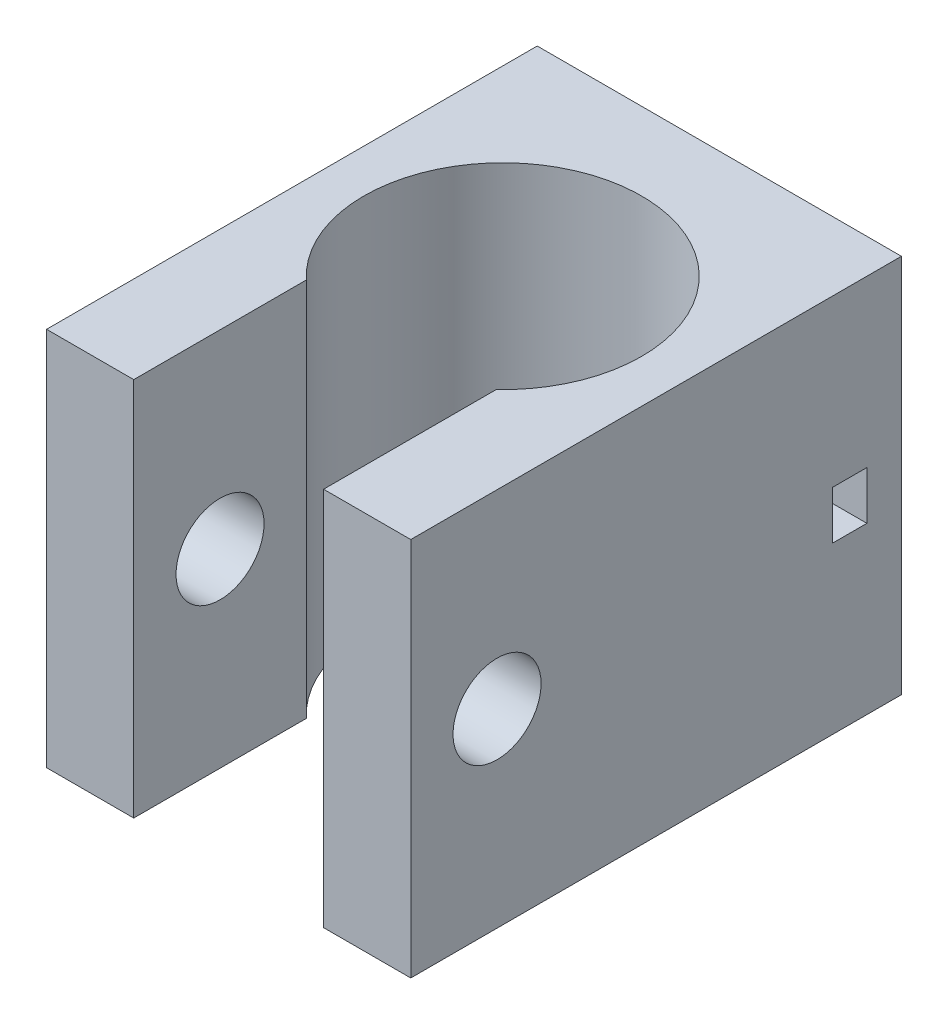
SolidWorks part; units mm, degrees
ref_plane "Front Plane" through (0, 0, 0) normal (0, 0, 1) x (1, 0, 0)
ref_plane "Top Plane" through (0, 0, 0) normal (0, 1, 0) x (1, 0, 0)
ref_plane "Right Plane" through (0, 0, 0) normal (1, 0, 0) x (0, 0, -1)
sketch "Sketch1" plane through (0, 0, 0) normal (0, 1, 0) x (1, 0, 0)
  line L0 (-5.5, -15) -> (-10.55, -15)
  line L1 (-10.55, -15) -> (-10.55, 13.4281)
  line L2 (-10.55, 13.4281) -> (10.55, 13.4281)
  line L3 (10.55, 13.4281) -> (10.55, -15)
  line L4 (10.55, -15) -> (5.5, -15)
  line L5 (5.5, -15) -> (5.5, -5)
  line L6 (-5.5, -15) -> (-5.5, -5)
  line L7 (-44.2539, 0) -> (44.2539, 0) construction
  line L8 (0, -44.7868) -> (0, 44.7868) construction
  arc A0 (-5.5, -5) -> (5.5, -5) centre (0, 0.8781) cw
  dimension "D1" = 8.05
  dimension "D2" = 11
  dimension "D3" = 10
  dimension "D4" = 10
  dimension "D5" = 21.1
  dimension "D6" = 12.55
  dimension "D7" = 15
  dimension "D8" = 10.55
extrude "Boss-Extrude1" add sketch "Sketch1" along normal mid plane 22
sketch "Sketch2" plane through (10.55, 0, 0) normal (1, 0, 0) x (0, 0, -1)
  line L0 (55, 0) -> (-55, 0) construction
  line L1 (-15, 11) -> (-15, -11) construction
  circle A0 centre (-10, 0) radius 2.55
  dimension "D1" = 5
  dimension "D2" = 5.1
extrude "Cut-Extrude1" cut sketch "Sketch2" against normal up to surface (21.1 mm away) up to face at (-10.55, 0, 0.7859)
sketch "Sketch4" plane through (10.55, 0, 0) normal (1, 0, 0) x (0, 0, -1)
  line L1 (9.4281, 1.4) -> (11.4281, 1.4)
  line L2 (9.4281, 1.4) -> (9.4281, -1.4)
  line L3 (9.4281, -1.4) -> (11.4281, -1.4)
  line L4 (11.4281, 1.4) -> (11.4281, -1.4)
  line L5 (-15, 11) -> (13.4281, 11) construction
  line L7 (13.4281, 11) -> (13.4281, -11) construction
  point P6 (10.4281, 1.4)
  dimension "D1" = 2
  dimension "D2" = 2.8
  dimension "D3" = 9.6
  dimension "D4" = 2
extrude "Cut-Extrude3" cut sketch "Sketch4" against normal up to surface (21.1 mm away) up to face at (-10.55, 0, 7.45)
sketch "Sketch5" plane through (0, 0, -13.4281) normal (0, 0, -1) x (-1, 0, 0)
  line L0 (10.55, 11) -> (10.55, -11) construction
  line L1 (-2.5, 8.5) -> (2.5, 8.5)
  line L2 (-2.5, 8.5) -> (-2.5, 3.5)
  line L3 (-2.5, 3.5) -> (2.5, 3.5)
  line L4 (2.5, 8.5) -> (2.5, 3.5)
  line L5 (2.5, -3.5) -> (-2.5, -3.5)
  line L6 (2.5, -3.5) -> (2.5, -8.5)
  line L7 (2.5, -8.5) -> (-2.5, -8.5)
  line L8 (-2.5, -3.5) -> (-2.5, -8.5)
  line L10 (-10.55, 11) -> (10.55, 11) construction
  line L11 (-10.55, -11) -> (10.55, -11) construction
  dimension "D1" = 5
  dimension "D2" = 5
  dimension "D3" = 5
  dimension "D4" = 5
  dimension "D5" = 8.05
  dimension "D6" = 8.05
  dimension "D7" = 2.5
  dimension "D8" = 2.5
extrude "Cut-Extrude5" cut sketch "Sketch5" against normal blind 2
equation "\"Width\"=21.1"
equation "\"D5@Sketch1\"=\"Width\""
equation "\"D8@Sketch1\"=\"Width\"/2"
equation "\"D6@Sketch1\"=\"Width\"/2+2"
